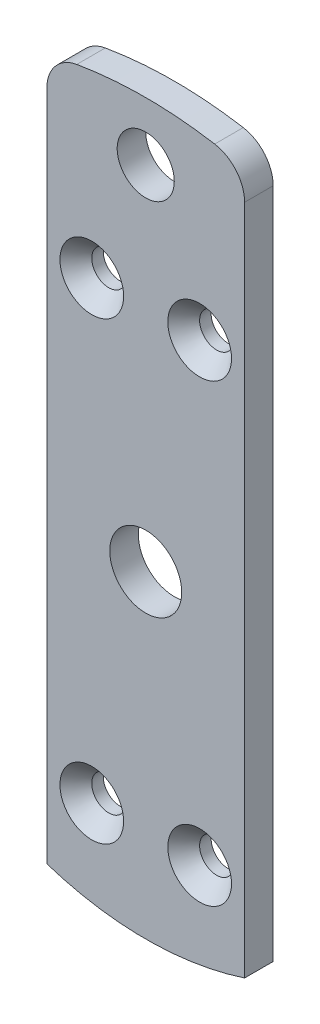
SolidWorks part; units mm, degrees
ref_plane "Front" through (0, 0, 0) normal (0, 0, 1) x (1, 0, 0)
ref_plane "Top" through (0, 0, 0) normal (0, 1, 0) x (1, 0, 0)
ref_plane "Right" through (0, 0, 0) normal (1, 0, 0) x (0, 0, -1)
ref_axis "side-side" through (80.9, 0, 0) along (-1, 0, 0)
ref_axis "up-down" through (0, 50, 0) along (0, -1, 0)
ref_axis "front-back" through (0, 0, -80.9) along (0, 0, 1)
sketch "Sketch1" plane through (0, 0, 0) normal (0, 0, 1) x (1, 0, 0)
  line L0 (0, 39.175) -> (0, 45.675) construction
  line L1 (0, 0) -> (-17.736, 0) construction
  line L2 (11, 44.3306) -> (11, -33.6476)
  line L3 (-11, -33.6476) -> (-11, 44.3306)
  line L4 (0, 0) -> (0, 24.2716) construction
  arc A1 (-11, -33.6476) -> (11, -33.6476) centre (0, 0) ccw
  arc A2 (-11, 44.3306) -> (11, 44.3306) centre (0, 0) cw
  circle A4 centre (0, 0) radius 4
  circle A5 centre (0, 39.175) radius 3.175
  point P4 (-6, -25.2982)
  point P5 (0, 0)
  point P8 (0, 0)
  dimension "D1" = 6.35
  dimension "D6" = 70.8
  dimension "D2" = 36
  dimension "D3" = 6.5
  dimension "D4" = 6
  dimension "D5" = 26
extrude "Boss-Extrude1" add sketch "Sketch1" along normal blind 3.175
hole_wizard "CSK for #6 Flat Head Machine Screw1" positions "Sketch2" profile "Sketch3" countersink size "#6" standard "ANSI Inch"
sketch "Sketch2" plane through (0, 0, 3.175) normal (0, 0, 1) x (1, 0, 0)
  line L0 (0, 0) -> (0, 23.6209) construction
  line L1 (0, 0) -> (22.6343, 0) construction
  point P0 (-6, 25.2982)
  point P3 (-6, -25.2982)
  point P6 (6, 25.2982)
  point P8 (6, -25.2982)
  point P21 (0, 0)
sketch "Sketch3" plane through (-6, 25.2982, 3.175) normal (1, 0, 0) x (0, -1, 0)
  line L0 (0, 0) -> (0, 12.1138)
  line L1 (0, 12.1138) -> (1.8986, 10.973)
  line L2 (1.8986, 10.973) -> (1.8986, 1.892)
  line L3 (1.8986, 1.892) -> (3.5433, 0)
  line L5 (3.5433, 0) -> (0, 0)
  line L6 (-1.8986, 1.892) -> (-3.5433, 0) construction
  line L10 (0, 12.1138) -> (-1.8987, 10.973) construction
  line L11 (0, -6.35) -> (0, 107.95) construction
  dimension "Hole Dia." = 3.7973
  dimension "Hole Depth" = 10.973
  dimension "Near C'Sink Dia." = 7.0866
  dimension "Near C'Sink Angle" = 82
  dimension "Drill Angle" = 118
fillet "Fillet1" radius 4 2 edges at (-11, 44.3306, 1.5875) (11, 44.3306, 1.5875)
